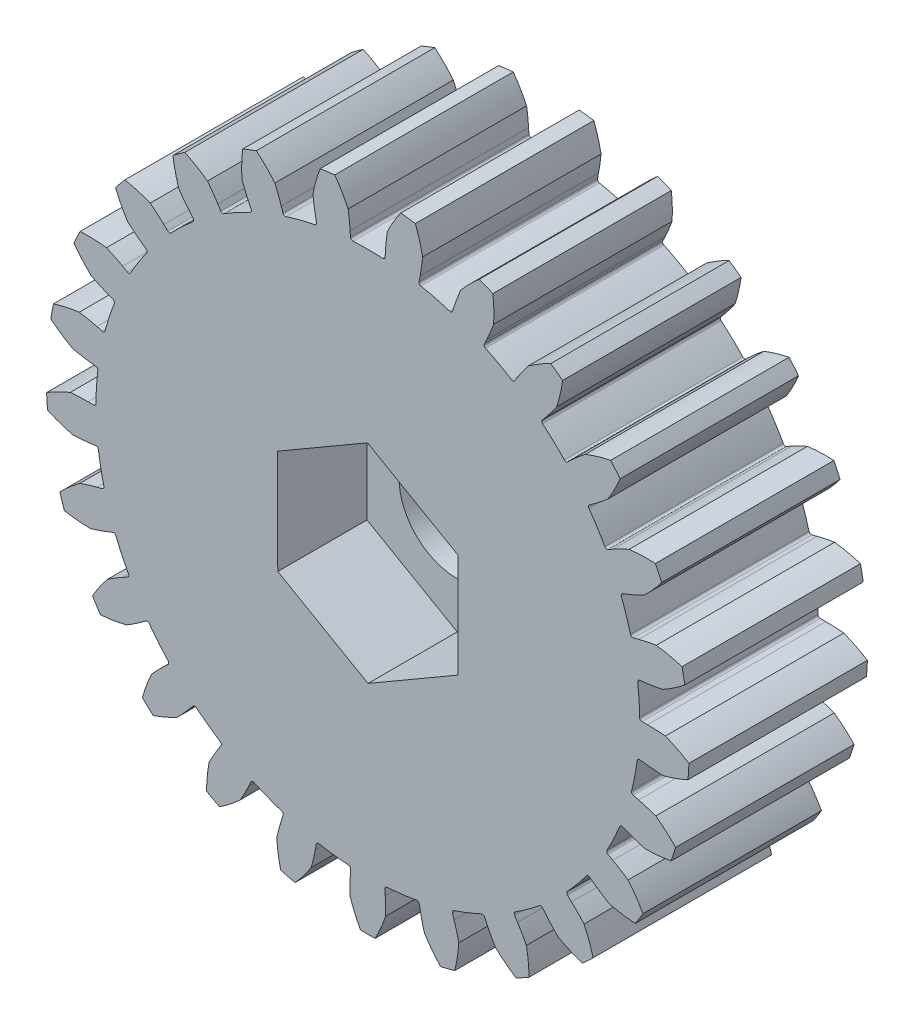
SolidWorks part; units mm, degrees
ref_plane "Plano frontal" through (0, 0, 0) normal (0, 0, 1) x (1, 0, 0)
ref_plane "Plano superior" through (0, 0, 0) normal (0, 1, 0) x (1, 0, 0)
ref_plane "Plano direito" through (0, 0, 0) normal (1, 0, 0) x (0, 0, -1)
sketch "Esboço1" plane through (0, 0, -10.2037) normal (0, 0, 1) x (1, 0, 0)
  circle A0 centre (175.26, 0) radius 7.14
  circle A1 centre (175.26, 0) radius 18.009
  circle A2 centre (175.26, 0) radius 7.14 construction
  circle A3 centre (175.26, 0) radius 7.14 construction
  dimension "D1" = 36.018
extrude "Ressalto-extrusão1" add sketch "Esboço1" against normal up to surface (5 mm away) contours A0
extrude "Ressalto-extrusão2" add sketch "Esboço1<3>" along normal up to surface (10 mm away) contours A1
sketch "Esboço1<3>" plane through (0, 0, -10.2037) normal (0, 0, 1) x (1, 0, 0) same geometry as "Esboço1"
sketch "Esboço2" plane through (0, 0, -0.2037) normal (0, 0, 1) x (1, 0, 0)
  circle A0 centre (175.26, 0) radius 3.25
  dimension "D1" = 6.5
extrude "Corte-extrusão1" cut sketch "Esboço2" against normal through all
sketch "Esboço3" plane through (0, 0, -0.2037) normal (0, 0, 1) x (1, 0, 0)
  line L0 (175.26, 0) -> (175.26, 18.009) construction
  line L2 (176.2304, 15.3293) -> (176.25, 15.6382)
  line L4 (174.27, 15.6382) -> (174.2896, 15.3293)
  circle A0 centre (175.26, 0) radius 15.2305 construction
  circle A1 centre (175.26, 0) radius 15.6695 construction
  circle A2 centre (175.26, 0) radius 16.675 construction
  circle A3 centre (175.26, 0) radius 18.009 construction
  arc A4 (174.27, 15.6382) -> (174.16, 16.6387) centre (163.4148, 14.951) ccw
  arc A5 (174.16, 16.6387) -> (173.4126, 17.914) centre (166.6756, 13.1088) ccw
  arc A6 (176.25, 15.6382) -> (176.36, 16.6387) centre (187.1052, 14.951) cw
  arc A7 (176.36, 16.6387) -> (177.1074, 17.914) centre (183.8444, 13.1088) cw
  arc A8 (174.4264, 15.2077) -> (176.0936, 15.2077) centre (175.26, 0) cw
  arc A10 (174.4264, 15.2077) -> (174.2896, 15.3293) centre (174.4193, 15.3375) cw
  arc A11 (176.0936, 15.2077) -> (176.2304, 15.3293) centre (176.1007, 15.3375) ccw
  arc A12 (173.4126, 17.914) -> (177.1074, 17.914) centre (175.26, 0) cw
  point P38 (174.2977, 15.2001)
  point P41 (176.2223, 15.2001)
  dimension "D1" = 30.461
  dimension "D2" = 33.35
  dimension "D3" = 31.339
  dimension "D5" = 1.98
  dimension "D6" = 0.13
  dimension "D7" = 8.275
  dimension "D4" = 2.2
extrude "Corte-extrusão2" cut sketch "Esboço3" against normal blind 10
pattern_circular "PadrãoCircular1" count 25 over 360 about axis through (175.26, 0, -0.2037) along (0, 0, -1) of "Corte-extrusão2"
sketch "Esboço4" plane through (0, 0, -0.2037) normal (0, 0, 1) x (1, 0, 0)
  line L1 (175.2467, 5.8312) -> (170.2034, 2.9041)
  line L2 (170.2034, 2.9041) -> (170.2167, -2.9271)
  line L3 (170.2167, -2.9271) -> (175.2733, -5.8312)
  line L4 (175.2733, -5.8312) -> (180.3166, -2.9041)
  line L5 (180.3166, -2.9041) -> (180.3033, 2.9271)
  line L6 (180.3033, 2.9271) -> (175.2467, 5.8312)
  circle A0 centre (175.26, 0) radius 5.05 construction
  dimension "D1" = 10.1
extrude "Corte-extrusão3" cut sketch "Esboço4" against normal blind 5
